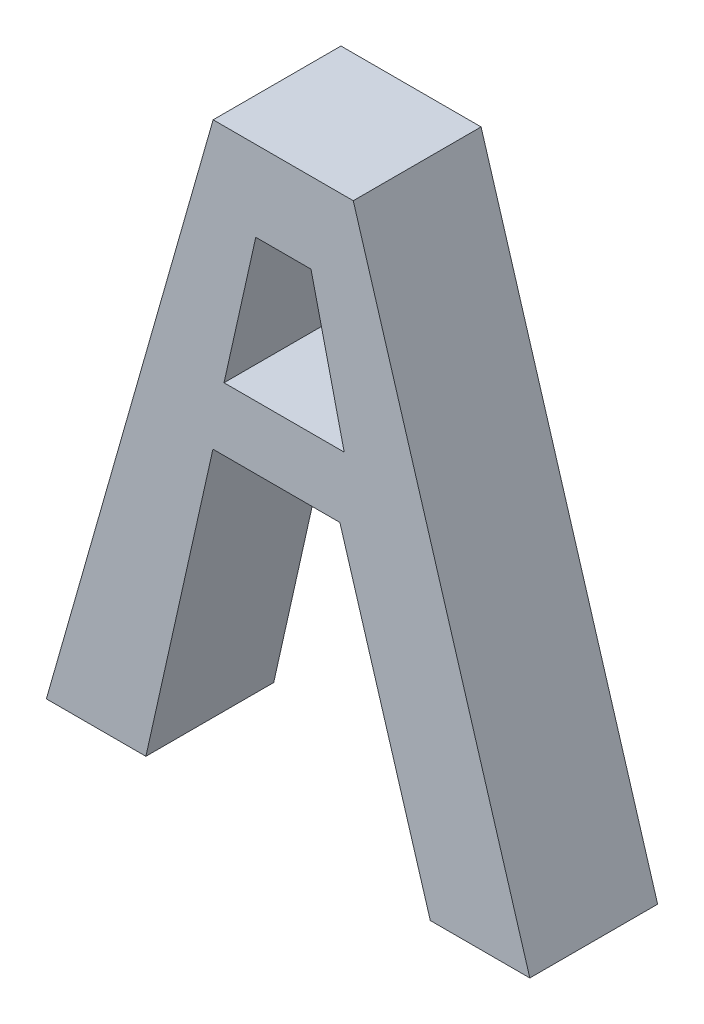
SolidWorks part; units mm, degrees
ref_plane "Front Plane" through (0, 0, 0) normal (0, 0, 1) x (1, 0, 0)
ref_plane "Top Plane" through (0, 0, 0) normal (0, 1, 0) x (1, 0, 0)
ref_plane "Right Plane" through (0, 0, 0) normal (1, 0, 0) x (0, 0, -1)
sketch "Sketch6" plane through (0, 0, 0) normal (0, 0, 1) x (1, 0, 0)
  line L0 (-115.2512, 64.6356) -> (-148.9082, -51.9897)
  line L1 (-115.2512, 64.6356) -> (-78.8547, -51.9897)
  line L2 (-132.0797, 6.3229) -> (-97.0529, 6.3229)
  line L3 (-17.6516, 61.0869) -> (-49.1368, -49.3339)
  line L4 (-17.6516, 61.0869) -> (8.802, 61.0869)
  line L5 (8.802, 61.0869) -> (42.1337, -49.3339)
  line L6 (-17.6938, 7.2158) -> (-30.3478, -49.3339)
  line L7 (-17.6938, 7.2158) -> (6.2746, 7.2158)
  line L8 (6.2746, 7.2158) -> (23.3447, -49.3339)
  line L9 (23.3447, -49.3339) -> (42.1337, -49.3339)
  line L10 (-30.3478, -49.3339) -> (-49.1368, -49.3339)
  line L11 (-9.6028, 45.9077) -> (0.8201, 45.9077)
  line L12 (-9.6028, 45.9077) -> (-15.5968, 19.121)
  line L13 (-15.5968, 19.121) -> (7.0947, 19.121)
  line L14 (0.8201, 45.9077) -> (7.0947, 19.121)
extrude "Boss-Extrude2" add sketch "Sketch6" along normal blind 24.13 contours L10 L6 L7 L8 L9 L5 L4 L3 L11 L14 L13 L12 region at (-4.4248, 59.6543, 0)
